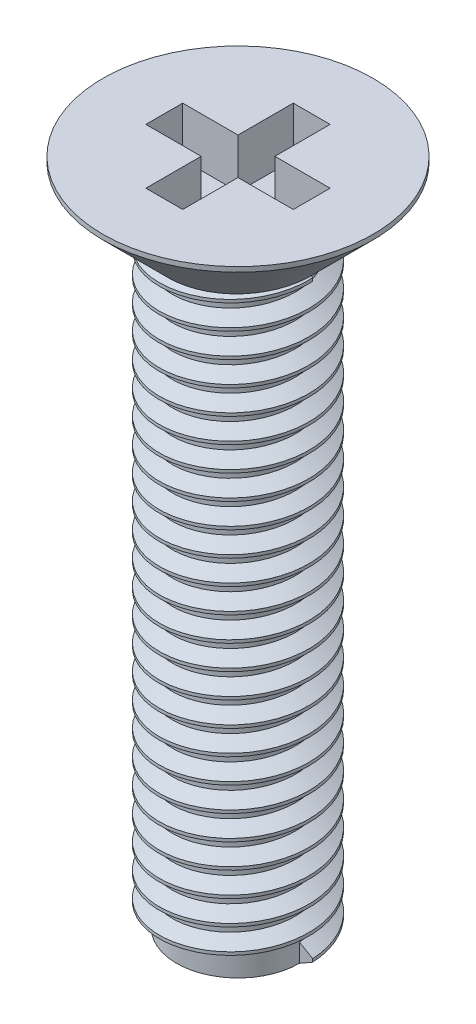
SolidWorks part; units mm, degrees
ref_plane "Front Plane" through (0, 0, 0) normal (0, 0, 1) x (1, 0, 0)
ref_plane "Top Plane" through (0, 0, 0) normal (0, 1, 0) x (1, 0, 0)
ref_plane "Right Plane" through (0, 0, 0) normal (1, 0, 0) x (0, 0, -1)
sketch "Sketch1" plane through (0, 0, 0) normal (0, 1, 0) x (1, 0, 0)
  circle A0 centre (0, 0) radius 1.25
  dimension "D1" = 2.5
extrude "Boss-Extrude1" add sketch "Sketch1" against normal blind 12
sketch "Sketch2" plane through (0, 0, 0) normal (0, 1, 0) x (1, 0, 0)
  circle A0 centre (0, 0) radius 2.75
  dimension "D1" = 5.5
extrude "Boss-Extrude2" add sketch "Sketch2" along normal blind 1.6
chamfer "Chamfer2" distance 1.5 1 edges at (0, 0, 2.75)
thread "Thread1" pitch 0.5 start angle 0, offset 0, length 0, pitch 0.5, diameter 2.5
ref_plane "Plane1" through (1.25, -12, 0) normal (0, 0, 1) x (1, 0, 0)
sketch "Thread Profile1" plane through (1.25, -12, 0) normal (0, 0, 1) x (1, 0, 0)
  line L0 (0, 0) -> (0, 0.5) construction
  line L1 (0, 0) -> (0.2706, 0.1562)
  line L2 (0.2706, 0.1562) -> (0.2706, 0.2187)
  line L3 (0.2706, 0.2187) -> (0, 0.375)
  line L4 (0.2706, 0.1875) -> (0, 0.1875) construction
  line L11 (0, 0) -> (0, 0.375)
  point P2 (0, 0)
  dimension "Pitch" = 0.5
  dimension "Profile_Angle" = 60
  dimension "Profile_Land" = 0.0625
  dimension "Profile_Height" = 0.2706
sketch "Sketch6" plane through (0, 1.6, 0) normal (0, 1, 0) x (1, 0, 0)
  line L1 (-0.375, -1.5) -> (0.375, -1.5)
  line L2 (-0.375, -1.5) -> (-0.375, 1.5)
  line L3 (-0.375, 1.5) -> (0.375, 1.5)
  line L4 (0.375, -1.5) -> (0.375, 1.5)
  line L5 (-0.375, -1.5) -> (0.375, 1.5) construction
  line L6 (-0.375, 1.5) -> (0.375, -1.5) construction
  line L7 (-1.5, -0.375) -> (1.5, -0.375)
  line L8 (-1.5, -0.375) -> (-1.5, 0.375)
  line L9 (-1.5, 0.375) -> (1.5, 0.375)
  line L10 (1.5, -0.375) -> (1.5, 0.375)
  line L11 (-1.5, -0.375) -> (1.5, 0.375) construction
  line L12 (-1.5, 0.375) -> (1.5, -0.375) construction
  point P0 (0, 0)
  point P6 (0, 0)
  dimension "D1" = 0.75
  dimension "D2" = 0.75
  dimension "D3" = 3
  dimension "D4" = 3
extrude "Cut-Extrude1" cut sketch "Sketch6" against normal blind 1 contours L2 L9 L4 L3 | L9 L2 L7 L4 | L7 L10 L9 L4 | L7 L2 L1 L4 | L9 L8 L7 L2
